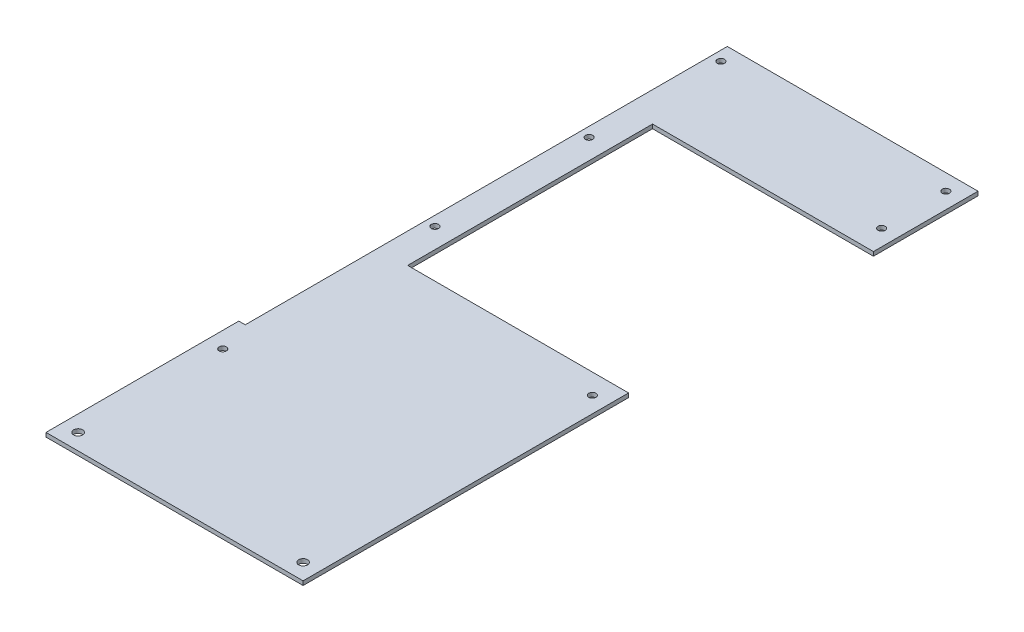
SolidWorks part; units mm, degrees
ref_plane "Front Plane" through (0, 0, 0) normal (1, 0, 0) x (0, 1, 0)
ref_plane "Top Plane" through (0, 0, 0) normal (0, 0, 1) x (0, 1, 0)
ref_plane "Right Plane" through (0, 0, 0) normal (0, 1, 0) x (-1, 0, 0)
sketch "Sketch1" plane through (0, 0, 0) normal (0, 1, 0) x (-1, 0, 0)
  line L0 (187.5, 235) -> (187.5, 275) construction
  line L1 (0, 275) -> (200, 275)
  line L2 (0, 275) -> (0, 525)
  line L3 (0, 525) -> (200, 525)
  line L4 (200, 275) -> (200, 525)
  line L5 (0, 275) -> (200, 525) construction
  line L6 (0, 525) -> (200, 275) construction
  line L7 (200, 275) -> (175, 275)
  line L8 (200, 275) -> (200, 0)
  line L9 (200, 0) -> (175, 0)
  line L10 (175, 275) -> (175, 0)
  line L11 (200, 275) -> (175, 0) construction
  line L12 (200, 0) -> (175, 275) construction
  line L13 (175, 0) -> (0, 0)
  line L14 (175, 0) -> (175, 75)
  line L15 (175, 75) -> (0, 75)
  line L16 (0, 0) -> (0, 75)
  line L17 (175, 0) -> (0, 75) construction
  line L18 (175, 75) -> (0, 0) construction
  line L19 (187.5, 115) -> (187.5, 0) construction
  line L20 (187.5, 512.5) -> (187.5, 235) construction
  circle A0 centre (12.5, 512.5) radius 3.5
  circle A1 centre (12.5, 287.5) radius 2.8
  circle A2 centre (187.5, 512.5) radius 3.5
  circle A3 centre (12.5, 62.5) radius 2.8
  circle A4 centre (12.5, 12.5) radius 2.8
  circle A5 centre (187.5, 12.5) radius 2.8
  circle A7 centre (187.5, 235) radius 2.8
  circle A8 centre (187.5, 115) radius 2.8
  circle A9 centre (187.5, 400) radius 2.8
  point P4 (100, 400)
  point P8 (187.5, 137.5)
  point P12 (87.5, 37.5)
  point P14 (0, 37.5)
  dimension "D7" = 5.6
  dimension "D22" = 7
  dimension "D1" = 25
  dimension "D2" = 250
  dimension "D3" = 200
  dimension "D4" = 200
  dimension "D5" = 200
  dimension "D6" = 75
  dimension "D8" = 12.5
  dimension "D9" = 12.5
  dimension "D10" = 12.5
  dimension "D11" = 12.5
  dimension "D12" = 12.5
  dimension "D13" = 12.5
  dimension "D14" = 12.5
  dimension "D15" = 12.5
  dimension "D16" = 12.5
  dimension "D17" = 12.5
  dimension "D18" = 12.5
  dimension "D19" = 12.5
  dimension "D20" = 40
  dimension "D21" = 40
  dimension "D23" = 125
extrude "Boss-Extrude1" add sketch "Sketch1" along normal blind 3.175 contours L1 L4 L3 L2 A2 A1 A0 | L1 L10 L9 L8 A8 A7 A5 | L16 L13 L10 L15 A4 A3 region at (-100, 0, 399.8819) region at (-187.5, 0, 137.6811) region at (-87.7825, 0, 37.5)
sketch "Sketch2" plane through (0, 3.175, 0) normal (0, 1, 0) x (-1, 0, 0)
  line L0 (175, 275) -> (175, 75) construction
  line L1 (0, 275) -> (175, 275)
  line L2 (0, 275) -> (0, 271.825)
  line L3 (0, 271.825) -> (175, 271.825)
  line L4 (175, 275) -> (175, 271.825)
  line L5 (0, 275) -> (175, 271.825) construction
  line L6 (0, 271.825) -> (175, 275) construction
  line L7 (175, 75) -> (0, 75) construction
  line L8 (175, 271.825) -> (171.825, 271.825)
  line L9 (175, 271.825) -> (175, 75)
  line L10 (175, 75) -> (171.825, 75)
  line L11 (171.825, 271.825) -> (171.825, 75)
  line L12 (175, 271.825) -> (171.825, 75) construction
  line L13 (175, 75) -> (171.825, 271.825) construction
  line L15 (0, 75) -> (171.825, 75)
  line L16 (0, 75) -> (0, 81.35)
  line L17 (0, 81.35) -> (171.825, 81.35)
  line L18 (171.825, 75) -> (171.825, 81.35)
  line L19 (0, 75) -> (171.825, 81.35) construction
  line L20 (0, 81.35) -> (171.825, 75) construction
  point P4 (87.5, 273.4125)
  point P11 (173.4125, 173.4125)
  point P17 (85.9125, 78.175)
  line M9 (0, 275) -> (175, 275)
  line M10 (175, 275) -> (175, 75)
  line M11 (175, 75) -> (0, 75)
  dimension "D1" = 3.175
  dimension "D2" = 3.175
  dimension "D3" = 6.35
extrude "Boss-Extrude2" add sketch "Sketch2" against normal through all contours L2 L3 M10 M9 | L3 L11 M11 M10 | L17 L16 L11 M11 region at (-87.5, 3.175, 273.4125) region at (-173.4125, 3.175, 173.4125) region at (-85.9125, 3.175, 78.175)
sketch "Sketch3" plane through (0, 3.175, 0) normal (0, 1, 0) x (-1, 0, 0)
  line L0 (200, 0) -> (0, 0) construction
  line L1 (200, 525) -> (195, 525)
  line L2 (200, 525) -> (200, 0)
  line L3 (200, 0) -> (195, 0)
  line L4 (195, 525) -> (195, 0)
  line L5 (200, 525) -> (195, 0) construction
  line L6 (200, 0) -> (195, 525) construction
  point P4 (197.5, 262.5)
  dimension "D1" = 5
extrude "Cut-Extrude1" cut sketch "Sketch3" against normal through all
sketch "Sketch4" plane through (0, 3.175, 0) normal (0, 1, 0) x (-1, 0, 0)
  line L1 (195, 525) -> (200, 525)
  line L2 (195, 525) -> (195, 375)
  line L3 (195, 375) -> (200, 375)
  line L4 (200, 525) -> (200, 375)
  line L5 (195, 525) -> (200, 375) construction
  line L6 (195, 375) -> (200, 525) construction
  point P4 (197.5, 450)
  dimension "D1" = 5
  dimension "D2" = 150
extrude "Boss-Extrude3" add sketch "Sketch4" against normal through all
